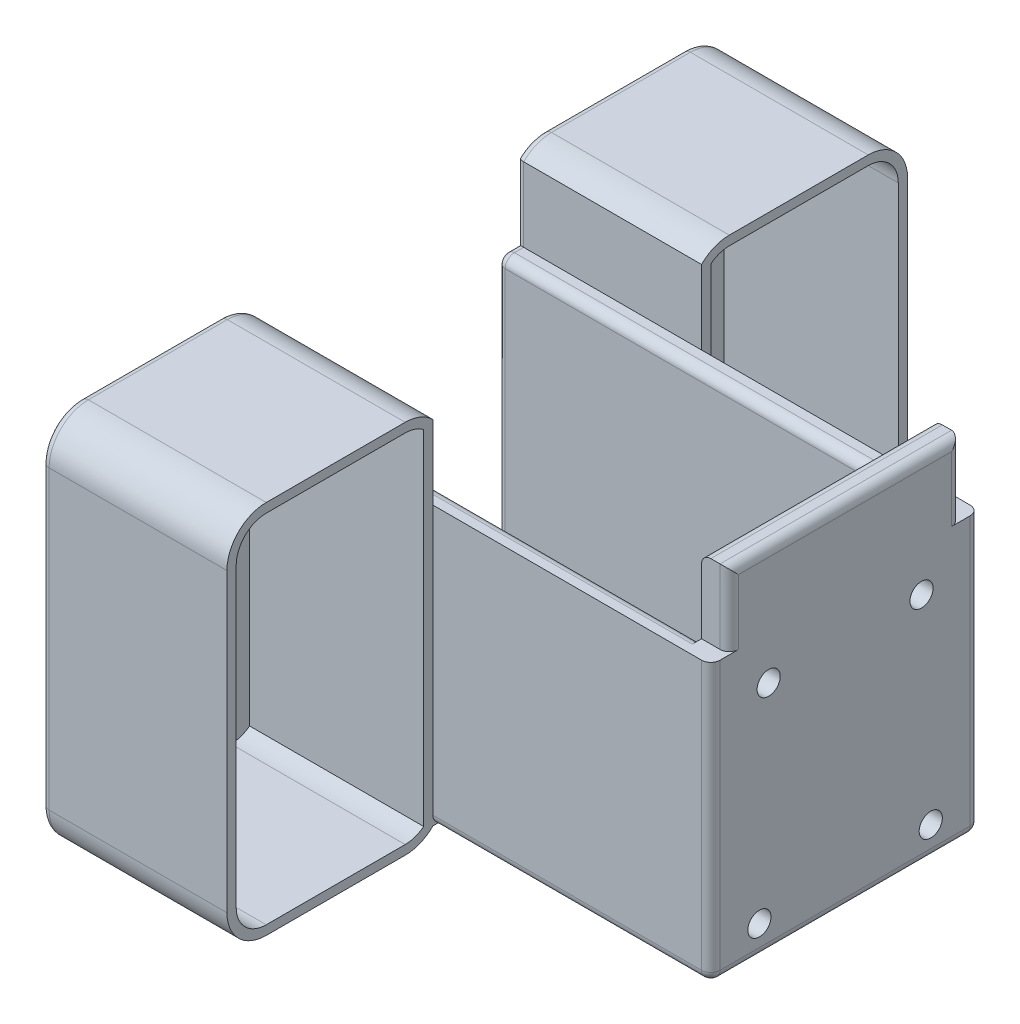
SolidWorks part; units mm, degrees
other "标注1"
sketch "草图6" plane through (3, -20.2426, 36.7426) normal (0.5, -0.866, 0) x (0, 0, -1)
ref_plane "前视基准面" through (0, 0, 0) normal (0, 0, 1) x (1, 0, 0)
ref_plane "上视基准面" through (0, 0, 0) normal (0, 1, 0) x (1, 0, 0)
ref_plane "右视基准面" through (0, 0, 0) normal (1, 0, 0) x (0, 0, -1)
sketch "草图1" plane through (0, 0, 0) normal (1, 0, 0) x (0, 0, -1)
  line L0 (0, 20.9) -> (0, -20.9) construction
  line L1 (-12.5, -19) -> (12.5, -19)
  line L2 (-12.5, -19) -> (-12.5, 19)
  line L3 (-12.5, 19) -> (12.5, 19)
  line L4 (12.5, -19) -> (12.5, 19)
  line L5 (-12.5, -19) -> (12.5, 19) construction
  line L6 (-12.5, 19) -> (12.5, -19) construction
  circle A0 centre (9.25, -15.75) radius 1.25
  circle A1 centre (8.25, 6.25) radius 1.25
  circle A2 centre (-9.25, -15.75) radius 1.25
  circle A3 centre (-8.25, 6.25) radius 1.25
  point P0 (0, 0)
  point P7 (0, 0)
  point P11 (0, 0)
  point P12 (0, 0)
extrude "凸台-拉伸2" add sketch "草图1" along normal blind 3
sketch "草图2" plane through (3, 0, 0) normal (1, 0, 0) x (0, 0, -1)
  line L0 (12.5, -19) -> (12.5, 19) construction
  line L1 (12.5, 11) -> (14.5, 11)
  line L2 (12.5, 11) -> (12.5, -19)
  line L3 (12.5, -19) -> (14.5, -19)
  line L4 (14.5, 11) -> (14.5, -19)
  line L5 (0, 1.65) -> (0, -1.65) construction
  line L6 (-12.5, -19) -> (-14.5, -19)
  line L7 (-14.5, 11) -> (-14.5, -19)
  line L8 (-12.5, 11) -> (-14.5, 11)
  line L9 (-12.5, 11) -> (-12.5, -19)
extrude "凸台-拉伸3" add sketch "草图2" against normal blind 50
sketch "草图4" plane through (-47, 0, 0) normal (-1, 0, 0) x (0, 0, 1)
  line L0 (-32.5, 19.2426) -> (-25, 19.2426)
  line L18 (-14.5, 11) -> (-14.5, 19)
  line L24 (0, -22.2669) -> (0, 22.2669) construction
  line L25 (-17.5, 20.2426) -> (-32.5, 20.2426)
  line L27 (-36.7426, -16) -> (-36.7426, 16)
  line L29 (-32.5, -20.2426) -> (-17.5, -20.2426)
  line L31 (-14.5, -19) -> (-14.5, 11)
  line L32 (35.7426, -12.0355) -> (35.7426, 16)
  line L33 (-35.7426, -16) -> (-35.7426, -12.0355)
  line L34 (-31.5031, -19.2426) -> (-32.5, -19.2426)
  line L35 (25, 19.2426) -> (17.5, 19.2426)
  line L36 (15.5, -12.0355) -> (15.5, 18.5524)
  line L37 (-15.5, -18.5524) -> (-15.5, -12.0355)
  line L38 (-31.5031, -19.2426) -> (-17.5, -19.2426)
  line L39 (-15.5, -12.0355) -> (-15.5, 18.5524)
  line L40 (31.5031, -19.2426) -> (17.5, -19.2426)
  line L41 (-25, 19.2426) -> (-17.5, 19.2426)
  line L43 (-35.7426, -12.0355) -> (-35.7426, 16)
  line L44 (15.5, -18.5524) -> (15.5, -12.0355)
  line L45 (31.5031, -19.2426) -> (32.5, -19.2426)
  line L46 (35.7426, -16) -> (35.7426, -12.0355)
  line L47 (14.5, -19) -> (14.5, 11)
  line L48 (32.5, -20.2426) -> (17.5, -20.2426)
  line L49 (36.7426, -16) -> (36.7426, 16)
  line L50 (17.5, 20.2426) -> (32.5, 20.2426)
  line L51 (14.5, 11) -> (14.5, 19)
  line L52 (32.5, 19.2426) -> (25, 19.2426)
  arc A9 (-17.5, 20.2426) -> (-14.5, 19) centre (-17.5, 16) cw
  arc A10 (-36.7426, 16) -> (-32.5, 20.2426) centre (-32.5, 16) cw
  arc A11 (-32.5, -20.2426) -> (-36.7426, -16) centre (-32.5, -16) cw
  arc A12 (-32.5, 19.2426) -> (-35.7426, 16) centre (-32.5, 16) ccw
  arc A13 (-35.7426, -16) -> (-32.5, -19.2426) centre (-32.5, -16) ccw
  arc A14 (-15.5, 18.5524) -> (-17.5, 19.2426) centre (-17.5, 16) ccw
  arc A15 (-17.5, -19.2426) -> (-15.5, -18.5524) centre (-17.5, -16) ccw
  arc A16 (-17.5, -20.2426) -> (-14.5, -19) centre (-17.5, -16) ccw
  arc A17 (17.5, -20.2426) -> (14.5, -19) centre (17.5, -16) cw
  arc A18 (17.5, -19.2426) -> (15.5, -18.5524) centre (17.5, -16) cw
  arc A19 (15.5, 18.5524) -> (17.5, 19.2426) centre (17.5, 16) cw
  arc A20 (35.7426, -16) -> (32.5, -19.2426) centre (32.5, -16) cw
  arc A21 (32.5, 19.2426) -> (35.7426, 16) centre (32.5, 16) cw
  arc A22 (32.5, -20.2426) -> (36.7426, -16) centre (32.5, -16) ccw
  arc A23 (36.7426, 16) -> (32.5, 20.2426) centre (32.5, 16) ccw
  arc A24 (17.5, 20.2426) -> (14.5, 19) centre (17.5, 16) ccw
extrude "凸台-拉伸6" add sketch "草图4" against normal blind 20
sketch "草图5" plane through (-47, 0, 0) normal (-1, 0, 0) x (0, 0, 1)
  line L1 (-32.5, 19.2426) -> (-17.5, 19.2426)
  line L2 (-17.5, 19.2426) -> (-32.5, 19.2426) construction
  line L4 (-15.5, 18.5524) -> (-15.5, -18.5524)
  line L6 (-17.5, -19.2426) -> (-32.5, -19.2426)
  line L8 (-35.7426, 16) -> (-35.7426, -16) construction
  line L9 (-35.7426, -16) -> (-35.7426, 16)
  line L10 (0, -22.2669) -> (0, 22.2669) construction
  line L11 (35.7426, -16) -> (35.7426, 16)
  line L12 (17.5, -19.2426) -> (32.5, -19.2426)
  line L13 (15.5, 18.5524) -> (15.5, -18.5524)
  line L14 (32.5, 19.2426) -> (17.5, 19.2426)
  arc A0 (-15.5, 18.5524) -> (-17.5, 19.2426) centre (-17.5, 16) ccw construction
  arc A1 (-35.7426, -16) -> (-32.5, -19.2426) centre (-32.5, -16) ccw construction
  arc A2 (-32.5, 19.2426) -> (-35.7426, 16) centre (-32.5, 16) ccw
  arc A3 (-35.7426, -16) -> (-32.5, -19.2426) centre (-32.5, -16) ccw
  arc A4 (-17.5, -19.2426) -> (-15.5, -18.5524) centre (-17.5, -16) ccw
  arc A5 (-15.5, 18.5524) -> (-17.5, 19.2426) centre (-17.5, 16) ccw
  arc A6 (15.5, 18.5524) -> (17.5, 19.2426) centre (17.5, 16) cw
  arc A7 (17.5, -19.2426) -> (15.5, -18.5524) centre (17.5, -16) cw
  arc A8 (35.7426, -16) -> (32.5, -19.2426) centre (32.5, -16) cw
  arc A9 (32.5, 19.2426) -> (35.7426, 16) centre (32.5, 16) cw
extrude "凸台-拉伸7" add sketch "草图5" against normal blind 1.2
fillet "圆角4" radius 1 13 edges at (-23.5, -19, 12.5) (-12, -19, 14.5) (-12, -19, -14.5) (0, -19, 0) (0, 19, 0) (-23.5, 11, -12.5) (-23.5, 11, 12.5) (3, -19, 0) (3, 15, 12.5) (3, -4, 14.5) (3, -4, -14.5) (3, 15, -12.5) (3, 19, 0)
fillet "圆角5" radius 0.8 25 edges at (-47, -19.9197, 15.8764) (-47, -20.2426, 25) (-47, -19, 35.5) (-47, 19.9197, 15.8764) (-47, 20.2426, 25) (-47, 19, 35.5) (-47, -19, 14) (-47, -18.7071, 12.7929) (-47, 11, 14) (-47, 10.7071, 12.7929) (-47, -19, -13.5) (-47, -19.9197, -15.8764) (-47, -20.2426, -25) (-47, -19, -35.5) (-47, 0, -36.7426) (-47, 19, -35.5) (-47, 20.2426, -25) (-47, 19.9197, -15.8764) (-47, 15, -14.5) (-47, 11, -14) (-47, 10.7071, -12.7929) (-47, -4.5, -12.5) (-47, 0, 36.7426) (-47, 15, 14.5) (-47, -4, 12.5)
